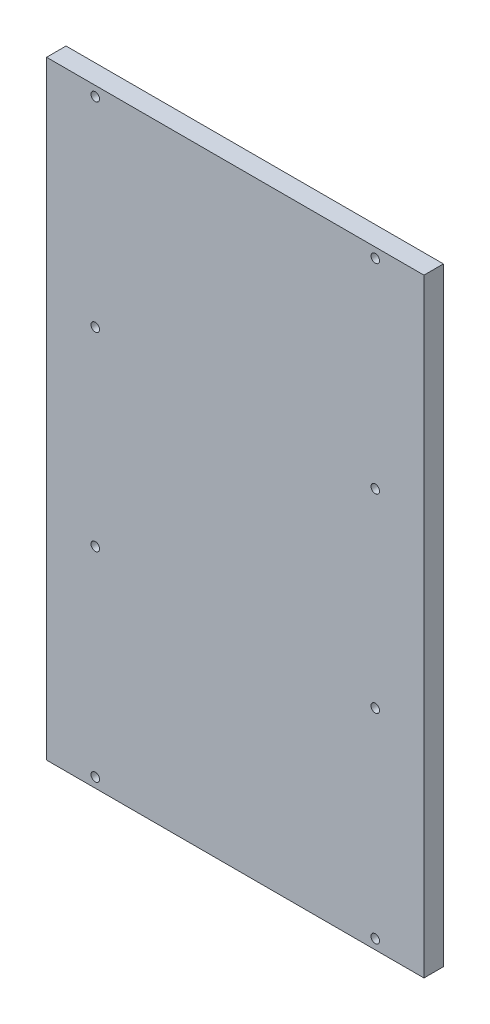
SolidWorks part; units mm, degrees
material "ДСП"
ref_plane "Спереди" through (0, 0, 0) normal (0, 0, 1) x (1, 0, 0)
ref_plane "Сверху" through (0, 0, 0) normal (0, 1, 0) x (1, 0, 0)
ref_plane "Справа" through (0, 0, 0) normal (1, 0, 0) x (0, 0, -1)
sketch "Эскиз1" plane through (0, 0, 0) normal (0, 0, 1) x (1, 0, 0)
  line L1 (0, 0) -> (310, 0)
  line L2 (0, 0) -> (0, 500)
  line L3 (0, 500) -> (310, 500)
  line L4 (310, 0) -> (310, 500)
  dimension "D1" = 500
  dimension "D2" = 310
extrude "Придание толщины" add sketch "Эскиз1" along normal blind 16
sketch "Эскиз3" plane through (0, 0, 16) normal (0, 0, 1) x (1, 0, 0)
  line L0 (0, 500) -> (0, 0) construction
  line L1 (0, 0) -> (310, 0) construction
  circle A0 centre (40, 8) radius 3.5
  dimension "D1" = 7
  dimension "D2" = 40
  dimension "D3" = 8
extrude "Отверстие 1" cut sketch "Эскиз3" against normal blind 16
sketch "Эскиз4" plane through (0, 0, 16) normal (0, 0, 1) x (1, 0, 0)
  line L0 (0, 500) -> (0, 0) construction
  line L1 (0, 0) -> (310, 0) construction
  circle A0 centre (270, 8) radius 3.5
  dimension "D3" = 7
  dimension "D1" = 270
  dimension "D2" = 8
extrude "Отверстие 2" cut sketch "Эскиз4" against normal blind 16
sketch "Эскиз5" plane through (0, 0, 16) normal (0, 0, 1) x (1, 0, 0)
  line L0 (0, 500) -> (0, 0) construction
  line L1 (0, 0) -> (310, 0) construction
  circle A0 centre (40, 492) radius 3.5
  dimension "D1" = 7
  dimension "D2" = 40
  dimension "D3" = 492
extrude "Отверстие 3" cut sketch "Эскиз5" against normal blind 16
sketch "Эскиз6" plane through (0, 0, 16) normal (0, 0, 1) x (1, 0, 0)
  line L0 (0, 500) -> (0, 0) construction
  line L1 (0, 0) -> (310, 0) construction
  circle A0 centre (270, 492) radius 3.5
  dimension "D1" = 7
  dimension "D3" = 492
  dimension "D2" = 270
extrude "Отверстие 4" cut sketch "Эскиз6" against normal blind 16
sketch "Эскиз7" plane through (0, 0, 16) normal (0, 0, 1) x (1, 0, 0)
  line L0 (0, 500) -> (0, 0) construction
  line L1 (0, 0) -> (310, 0) construction
  circle A0 centre (40, 172) radius 3.5
  dimension "D1" = 7
  dimension "D2" = 40
  dimension "D3" = 172
extrude "Отверстие 5" cut sketch "Эскиз7" against normal blind 16
sketch "Эскиз8" plane through (0, 0, 16) normal (0, 0, 1) x (1, 0, 0)
  line L0 (0, 500) -> (0, 0) construction
  line L1 (0, 0) -> (310, 0) construction
  circle A0 centre (270, 172) radius 3.5
  dimension "D1" = 7
  dimension "D2" = 270
  dimension "D3" = 172
extrude "Отверстие 6" cut sketch "Эскиз8" against normal blind 16
sketch "Эскиз9" plane through (0, 0, 16) normal (0, 0, 1) x (1, 0, 0)
  line L0 (0, 500) -> (0, 0) construction
  line L1 (0, 0) -> (310, 0) construction
  circle A0 centre (40, 328) radius 3.5
  dimension "D1" = 7
  dimension "D2" = 40
  dimension "D3" = 328
extrude "Отверстие 7" cut sketch "Эскиз9" against normal blind 16
sketch "Эскиз10" plane through (0, 0, 16) normal (0, 0, 1) x (1, 0, 0)
  line L0 (0, 500) -> (0, 0) construction
  line L1 (0, 0) -> (310, 0) construction
  circle A0 centre (270, 328) radius 3.5
  dimension "D1" = 7
  dimension "D2" = 270
  dimension "D3" = 328
extrude "Отверстие 8" cut sketch "Эскиз10" against normal blind 16
sketch "Эскиз27" plane through (0, 0, 16) normal (0, 0, 1) x (1, 0, 0)
  line L2 (0, 500) -> (0, 0) construction
  line L3 (0, 0) -> (310, 0) construction
  circle A0 centre (0, 0) radius 4
  dimension "D3" = 0
  dimension "D1" = 8
extrude "Отверстие 9" [suppressed] cut sketch "Эскиз27" against normal blind 10
sketch "Эскиз29" plane through (0, 0, 16) normal (0, 0, 1) x (1, 0, 0)
  line L2 (0, 500) -> (0, 0) construction
  line L3 (0, 0) -> (310, 0) construction
  circle A0 centre (0, 0) radius 4
  dimension "D1" = 8
extrude "Отверстие 10" [suppressed] cut sketch "Эскиз29" against normal blind 10
sketch "Эскиз30" plane through (0, 0, 16) normal (0, 0, 1) x (1, 0, 0)
  line L1 (0, 0) -> (310, 0) construction
  line L3 (0, 500) -> (0, 0) construction
  circle A0 centre (0, 0) radius 4
  dimension "D1" = 8
extrude "Отверстие 11" [suppressed] cut sketch "Эскиз30" against normal blind 10
sketch "Эскиз31" plane through (0, 0, 16) normal (0, 0, 1) x (1, 0, 0)
  line L2 (0, 0) -> (310, 0) construction
  line L3 (0, 500) -> (0, 0) construction
  circle A0 centre (0, 0) radius 4
  dimension "D1" = 8
extrude "Отверстие 12" [suppressed] cut sketch "Эскиз31" against normal blind 10
sketch "Эскиз11" plane through (0, 500, 0) normal (0, 1, 0) x (1, 0, 0)
  line L0 (0, -16) -> (0, 0) construction
  line L1 (310, -16) -> (0, -16) construction
  circle A0 centre (0, -16) radius 2.5
  dimension "D1" = 5
  dimension "D3" = 0
extrude "Отверстие А1" [suppressed] cut sketch "Эскиз11" against normal blind 37
sketch "Эскиз12" plane through (0, 500, 0) normal (0, 1, 0) x (1, 0, 0)
  line L1 (0, -16) -> (0, 0) construction
  line L2 (310, -16) -> (0, -16) construction
  circle A0 centre (0, -16) radius 2.5
  dimension "D1" = 5
  dimension "D3" = 0
extrude "Отверстие А2" [suppressed] cut sketch "Эскиз12" against normal blind 37
sketch "Эскиз13" plane through (0, 500, 0) normal (0, 1, 0) x (1, 0, 0)
  line L1 (0, -16) -> (0, 0) construction
  line L2 (310, -16) -> (0, -16) construction
  circle A0 centre (0, -16) radius 4
  dimension "D3" = 0
  dimension "D1" = 8
extrude "Отверстие А3" [suppressed] cut sketch "Эскиз13" against normal blind 20
sketch "Эскиз14" plane through (0, 500, 0) normal (0, 1, 0) x (1, 0, 0)
  line L0 (0, -16) -> (0, 0) construction
  line L1 (310, -16) -> (0, -16) construction
  circle A0 centre (0, -8) radius 4
  dimension "D3" = 8
  dimension "D1" = 8
extrude "Отверстие А4" [suppressed] cut sketch "Эскиз14" against normal blind 20
sketch "Эскиз15" plane through (310, 0, 0) normal (1, 0, 0) x (0, 0, -1)
  line L0 (-16, 500) -> (0, 500) construction
  line L1 (-16, 0) -> (-16, 500) construction
  circle A0 centre (-16, 500) radius 2.5
  dimension "D1" = 5
  dimension "D2" = 0
  dimension "D3" = 0
extrude "Отверстие В1" [suppressed] cut sketch "Эскиз15" against normal blind 37
sketch "Эскиз16" plane through (310, 0, 0) normal (1, 0, 0) x (0, 0, -1)
  line L0 (-16, 500) -> (0, 500) construction
  line L1 (-16, 0) -> (-16, 500) construction
  circle A0 centre (-16, 500) radius 2.5
  dimension "D1" = 5
extrude "Отверстие В2" [suppressed] cut sketch "Эскиз16" against normal blind 37
sketch "Эскиз17" plane through (310, 0, 0) normal (1, 0, 0) x (0, 0, -1)
  line L1 (-16, 500) -> (0, 500) construction
  line L2 (-16, 0) -> (-16, 500) construction
  circle A0 centre (-16, 500) radius 4
  dimension "D2" = 0
  dimension "D3" = 0
  dimension "D1" = 8
extrude "Отверстие В3" [suppressed] cut sketch "Эскиз17" against normal blind 20
sketch "Эскиз18" plane through (310, 0, 0) normal (1, 0, 0) x (0, 0, -1)
  line L0 (-16, 500) -> (0, 500) construction
  line L1 (-16, 0) -> (-16, 500) construction
  circle A0 centre (-16, 500) radius 4
  dimension "D2" = 8
  dimension "D3" = 0
  dimension "D1" = 0
extrude "Отверстие В4" [suppressed] cut sketch "Эскиз18" against normal blind 20
sketch "Эскиз19" plane through (0, 0, 0) normal (0, -1, 0) x (1, 0, 0)
  line L0 (310, 16) -> (310, 0) construction
  line L1 (0, 16) -> (310, 16) construction
  circle A0 centre (310, 16) radius 2.5
  dimension "D1" = 5
  dimension "D2" = 0
  dimension "D3" = 0
extrude "Отверстие С1" [suppressed] cut sketch "Эскиз19" against normal blind 37
sketch "Эскиз20" plane through (0, 0, 0) normal (0, -1, 0) x (1, 0, 0)
  line L0 (310, 16) -> (310, 0) construction
  line L1 (0, 16) -> (310, 16) construction
  circle A0 centre (310, 16) radius 2.5
  dimension "D3" = 0
  dimension "D1" = 0
  dimension "D2" = 5
extrude "Отверстие С2" [suppressed] cut sketch "Эскиз20" against normal blind 37
sketch "Эскиз21" plane through (0, 0, 0) normal (0, -1, 0) x (1, 0, 0)
  line L0 (310, 16) -> (310, 0) construction
  line L1 (0, 16) -> (310, 16) construction
  circle A0 centre (310, 16) radius 4
  dimension "D2" = 0
  dimension "D3" = 0
  dimension "D1" = 8
extrude "Отверстие С3" [suppressed] cut sketch "Эскиз21" against normal blind 20
sketch "Эскиз22" plane through (0, 0, 0) normal (0, -1, 0) x (1, 0, 0)
  line L0 (310, 16) -> (310, 0) construction
  line L1 (0, 16) -> (310, 16) construction
  circle A0 centre (310, 16) radius 4
  dimension "D2" = 0
  dimension "D3" = 0
  dimension "D1" = 8
extrude "Отверстие С4" [suppressed] cut sketch "Эскиз22" against normal blind 20
sketch "Эскиз23" plane through (0, 0, 0) normal (-1, 0, 0) x (0, 0, 1)
  line L0 (16, 0) -> (0, 0) construction
  line L1 (16, 500) -> (16, 0) construction
  circle A0 centre (16, 0) radius 2.5
  dimension "D1" = 5
  dimension "D2" = 0
  dimension "D3" = 0
extrude "Отверстие Д1" [suppressed] cut sketch "Эскиз23" against normal blind 37
sketch "Эскиз24" plane through (0, 0, 0) normal (-1, 0, 0) x (0, 0, 1)
  line L0 (16, 0) -> (0, 0) construction
  line L1 (16, 500) -> (16, 0) construction
  circle A0 centre (16, 0) radius 2.5
  dimension "D1" = 5
  dimension "D2" = 0
  dimension "D3" = 0
extrude "Отверстие Д2" [suppressed] cut sketch "Эскиз24" against normal blind 37
sketch "Эскиз25" plane through (0, 0, 0) normal (-1, 0, 0) x (0, 0, 1)
  line L0 (16, 0) -> (0, 0) construction
  line L1 (16, 500) -> (16, 0) construction
  circle A0 centre (16, 0) radius 4
  dimension "D2" = 0
  dimension "D3" = 0
  dimension "D1" = 8
extrude "Отверстие Д3" [suppressed] cut sketch "Эскиз25" against normal blind 20
sketch "Эскиз26" plane through (0, 0, 0) normal (-1, 0, 0) x (0, 0, 1)
  line L0 (16, 0) -> (0, 0) construction
  line L1 (16, 500) -> (16, 0) construction
  circle A0 centre (16, 0) radius 4
  dimension "D2" = 0
  dimension "D3" = 0
  dimension "D1" = 8
extrude "Отверстие Д4" [suppressed] cut sketch "Эскиз26" against normal blind 20
equation "\"D1@Придание толщины\" = \"Thick\""
equation "\"D2@Эскиз1\"=\"Width\""
equation "\"D1@Эскиз1\"=\"Height\""
equation "\"D1\" = 7"
equation "\"X1\" = 40"
equation "\"Y1\" = 8"
equation "\"H1\" = 16"
equation "\"D1@Эскиз3\"=\"D1\""
equation "\"D2@Эскиз3\"=\"X1\""
equation "\"D3@Эскиз3\"=\"Y1\""
equation "\"D1@Отверстие 1\"=\"H1\""
equation "\"D2\" = 7"
equation "\"X2\" = 270"
equation "\"Y2\" = 8"
equation "\"H2\" = 16"
equation "\"D3\" = 7"
equation "\"X3\" = 40"
equation "\"Y3\" = 492"
equation "\"H3\" = 16"
equation "\"D4\" = 7"
equation "\"X4\" = 270"
equation "\"Y4\" = 492"
equation "\"H4\" = 16"
equation "\"D5\" = 7"
equation "\"X5\" = 40"
equation "\"Y5\" = 172"
equation "\"H5\" = 16"
equation "\"D6\" = 7"
equation "\"X6\" = 270"
equation "\"Y6\" = 172"
equation "\"H6\" = 16"
equation "\"D7\" = 7"
equation "\"X7\" = 40"
equation "\"Y7\" = 328"
equation "\"H7\" = 16"
equation "\"D8\" = 7"
equation "\"X8\" = 270"
equation "\"Y8\" = 328"
equation "\"H8\" = 16"
equation "\"D3@Эскиз4\"=\"D2\""
equation "\"D1@Эскиз4\"=\"X2\""
equation "\"D2@Эскиз4\"=\"Y2\""
equation "\"D1@Отверстие 2\"=\"H2\""
equation "\"D2@Эскиз5\"=\"X3\""
equation "\"D1@Эскиз5\"=\"D3\""
equation "\"D3@Эскиз5\"=\"Y3\""
equation "\"D1@Отверстие 3\" = \"H3\""
equation "\"D1@Эскиз6\"=\"D4\""
equation "\"D2@Эскиз6\"=\"X4\""
equation "\"D3@Эскиз6\"=\"Y4\""
equation "\"D1@Отверстие 4\" = \"H4\""
equation "\"D1@Эскиз7\"=\"D5\""
equation "\"D2@Эскиз7\"=\"X5\""
equation "\"D3@Эскиз7\"=\"Y5\""
equation "\"D1@Отверстие 5\" = \"H5\""
equation "\"D1@Эскиз8\"=\"D6\""
equation "\"D2@Эскиз8\"=\"X6\""
equation "\"D3@Эскиз8\"=\"Y6\""
equation "\"D1@Отверстие 6\" = \"H6\""
equation "\"D1@Эскиз9\"=\"D7\""
equation "\"D2@Эскиз9\"=\"X7\""
equation "\"D3@Эскиз9\"=\"Y7\""
equation "\"D1@Отверстие 7\" = \"H7\""
equation "\"D1@Эскиз10\"=\"D8\""
equation "\"D2@Эскиз10\"=\"X8\""
equation "\"D3@Эскиз10\"=\"Y8\""
equation "\"D1@Отверстие 8\" = \"H8\""
equation "\"Отверстие 1\"= IIF ( \"D1\" = 0 , \"suppressed\" , \"unsuppressed\" )"
equation "\"Отверстие 2\"= IIF ( \"D2\" = 0 , \"suppressed\" , \"unsuppressed\" )"
equation "\"Отверстие 3\"= IIF ( \"D3\" = 0 , \"suppressed\" , \"unsuppressed\" )"
equation "\"Отверстие 4\"= IIF ( \"D4\" = 0 , \"suppressed\" , \"unsuppressed\" )"
equation "\"Отверстие 5\"= IIF ( \"D5\" = 0 , \"suppressed\" , \"unsuppressed\" )"
equation "\"Отверстие 6\" = IIF ( \"D6\" = 0 , \"suppressed\" , \"unsuppressed\" )"
equation "\"Отверстие 7\"= IIF ( \"D7\" = 0 , \"suppressed\" , \"unsuppressed\" )"
equation "\"Отверстие 8\"= IIF ( \"D8\" = 0 , \"suppressed\" , \"unsuppressed\" )"
equation "\"DA1\" = 0"
equation "\"XA1\" = 0"
equation "\"YA1\" = 0"
equation "\"HA1\" = 0"
equation "\"DA2\" = 0"
equation "\"XA2\" = 0"
equation "\"YA2\" = 0"
equation "\"HA2\" = 0"
equation "\"DA3\" = 0"
equation "\"XA3\" = 0"
equation "\"YA3\" = 0"
equation "\"DA4\" = 0"
equation "\"XA4\" = 0"
equation "\"YA4\" = 0"
equation "\"HA4\" = 0"
equation "\"D1@Эскиз11\"=\"DA1\""
equation "\"D2@Эскиз11\"=\"XA1\""
equation "\"D3@Эскиз11\"=\"YA1\""
equation "\"D1@Отверстие А1\" = \"HA1\""
equation "\"D1@Эскиз12\"=\"DA2\""
equation "\"D2@Эскиз12\"=\"XA2\""
equation "\"HA3\" = 0"
equation "\"D1@Эскиз13\"=\"DA3\""
equation "\"D2@Эскиз13\"=\"XA3\""
equation "\"D3@Эскиз13\"=\"YA3\""
equation "\"D1@Отверстие А3\" = \"HA3\""
equation "\"D1@Отверстие А2\" = \"HA2\""
equation "\"D1@Эскиз14\"=\"DA4\""
equation "\"D2@Эскиз14\"=\"XA4\""
equation "\"Отверстие А1\"= IIF ( \"DA1\" = 0 , \"suppressed\" , \"unsuppressed\" )"
equation "\"Отверстие А2\"= IIF ( \"DA2\" = 0 , \"suppressed\" , \"unsuppressed\" )"
equation "\"Отверстие А3\"= IIF ( \"DA3\" = 0 , \"suppressed\" , \"unsuppressed\" )"
equation "\"Отверстие А4\"= IIF ( \"DA4\" = 0 , \"suppressed\" , \"unsuppressed\" )"
equation "\"DB1\" = 0"
equation "\"XB1\" = 0"
equation "\"YB1\" = 0"
equation "\"HB1\" = 0"
equation "\"DB2\" = 0"
equation "\"XB2\" = 0"
equation "\"YB2\" = 0"
equation "\"HB2\" = 0"
equation "\"DB3\" = 0"
equation "\"XB3\" = 0"
equation "\"YB3\" = 0"
equation "\"HB3\" = 0"
equation "\"DB4\" = 0"
equation "\"XB4\" = 0"
equation "\"YB4\" = 0"
equation "\"HB4\" = 0"
equation "\"DC1\" = 0"
equation "\"XC1\" = 0"
equation "\"YC1\" = 0"
equation "\"HC1\" = 0"
equation "\"DC2\" = 0"
equation "\"XC2\" = 0"
equation "\"YC2\" = 0"
equation "\"HC2\" = 0"
equation "\"DC3\" = 0"
equation "\"XC3\" = 0"
equation "\"YC3\" = 0"
equation "\"HC3\" = 0"
equation "\"DC4\" = 0"
equation "\"XC4\" = 0"
equation "\"YC4\" = 0"
equation "\"HC4\" = 0"
equation "\"DD1\" = 0"
equation "\"XD1\" = 0"
equation "\"YD1\" = 0"
equation "\"HD1\" = 0"
equation "\"DD2\" = 0"
equation "\"XD2\" = 0"
equation "\"YD2\" = 0"
equation "\"HD2\" = 0"
equation "\"DD3\" = 0"
equation "\"XD3\" = 0"
equation "\"YD3\" = 0"
equation "\"HD3\" = 0"
equation "\"DD4\" = 0"
equation "\"XD4\" = 0"
equation "\"YD4\" = 0"
equation "\"HD4\" = 0"
equation "\"D1@Эскиз15\"=\"DB1\""
equation "\"D2@Эскиз15\"=\"XB1\""
equation "\"D3@Эскиз15\"=\"YB1\""
equation "\"D1@Отверстие В1\" = \"HB1\""
equation "\"D1@Эскиз16\"=\"DB2\""
equation "\"D2@Эскиз16\"=\"XB2\""
equation "\"D3@Эскиз16\"=\"YB2\""
equation "\"D1@Отверстие В2\" = \"HB2\""
equation "\"D1@Эскиз17\"=\"DB3\""
equation "\"D2@Эскиз17\"=\"XB3\""
equation "\"D3@Эскиз17\"=\"YB3\""
equation "\"D1@Отверстие В3\" = \"HB3\""
equation "\"D1@Эскиз18\"=\"XB4\""
equation "\"D2@Эскиз18\"=\"DB4\""
equation "\"D3@Эскиз18\"=\"YB4\""
equation "\"D1@Отверстие В4\" = \"HB4\""
equation "\"D1@Эскиз19\"=\"DC1\""
equation "\"D2@Эскиз19\"=\"XC1\""
equation "\"D3@Эскиз19\"=\"YC1\""
equation "\"D1@Отверстие С1\" = \"HC1\""
equation "\"D1@Эскиз20\"=\"XC2\""
equation "\"D2@Эскиз20\"=\"DC2\""
equation "\"D3@Эскиз20\"=\"YC2\""
equation "\"D1@Отверстие С2\" = \"HC2\""
equation "\"D1@Эскиз21\"=\"DC3\""
equation "\"D2@Эскиз21\"=\"XC3\""
equation "\"D3@Эскиз21\"=\"YC3\""
equation "\"D1@Отверстие С3\" = \"HC3\""
equation "\"D1@Эскиз22\"=\"DC4\""
equation "\"D2@Эскиз22\"=\"XC4\""
equation "\"D3@Эскиз22\"=\"YC4\""
equation "\"D1@Отверстие С4\" = \"HC4\""
equation "\"D1@Эскиз23\"=\"DD1\""
equation "\"D2@Эскиз23\"=\"XD1\""
equation "\"D3@Эскиз23\"=\"YD1\""
equation "\"D1@Отверстие Д1\" = \"HD1\""
equation "\"D1@Эскиз24\"=\"DD2\""
equation "\"D2@Эскиз24\"=\"XD2\""
equation "\"D3@Эскиз24\"=\"YD2\""
equation "\"D1@Отверстие Д2\" = \"HD2\""
equation "\"D1@Эскиз25\"=\"DD3\""
equation "\"D2@Эскиз25\"=\"XD3\""
equation "\"D3@Эскиз25\"=\"YD3\""
equation "\"D1@Отверстие Д3\" = \"HD3\""
equation "\"D1@Эскиз26\"=\"DD4\""
equation "\"D2@Эскиз26\"=\"XD4\""
equation "\"D3@Эскиз26\"=\"YD4\""
equation "\"D1@Отверстие Д4\" = \"HD4\""
equation "\"Отверстие В1\"= IIF ( \"DB1\" = 0 , \"suppressed\" , \"unsuppressed\" )"
equation "\"Отверстие В2\"= IIF ( \"DB2\" = 0 , \"suppressed\" , \"unsuppressed\" )"
equation "\"Отверстие В3\"= IIF ( \"DB3\" = 0 , \"suppressed\" , \"unsuppressed\" )"
equation "\"Отверстие В4\"= IIF ( \"DB4\" = 0 , \"suppressed\" , \"unsuppressed\" )"
equation "\"Отверстие С1\"= IIF ( \"DC1\" = 0 , \"suppressed\" , \"unsuppressed\" )"
equation "\"Отверстие С2\"= IIF ( \"DC2\" = 0 , \"suppressed\" , \"unsuppressed\" )"
equation "\"Отверстие С3\"= IIF ( \"DC3\" = 0 , \"suppressed\" , \"unsuppressed\" )"
equation "\"Отверстие С4\"= IIF ( \"DC4\" = 0 , \"suppressed\" , \"unsuppressed\" )"
equation "\"Отверстие Д1\"= IIF ( \"DD1\" = 0 , \"suppressed\" , \"unsuppressed\" )"
equation "\"Отверстие Д2\"= IIF ( \"DD2\" = 0 , \"suppressed\" , \"unsuppressed\" )"
equation "\"Отверстие Д3\"= IIF ( \"DD3\" = 0 , \"suppressed\" , \"unsuppressed\" )"
equation "\"Отверстие Д4\"= IIF ( \"DD4\" = 0 , \"suppressed\" , \"unsuppressed\" )"
equation "\"D9\" = 0"
equation "\"X9\" = 0"
equation "\"Y9\" = 0"
equation "\"H9\" = 0"
equation "\"D10\" = 0"
equation "\"X10\" = 0"
equation "\"Y10\" = 0"
equation "\"H10\" = 0"
equation "\"D11\" = 0"
equation "\"X11\" = 0"
equation "\"Y11\" = 0"
equation "\"H11\" = 0"
equation "\"D12\" = 0"
equation "\"X12\" = 0"
equation "\"Y12\" = 0"
equation "\"H12\" = 0"
equation "\"D1@Эскиз27\"=\"D9\""
equation "\"D2@Эскиз27\"=\"X9\""
equation "\"D3@Эскиз27\"=\"Y9\""
equation "\"D1@Отверстие 9\" = \"H9\""
equation "\"D1@Эскиз29\"=\"D10\""
equation "\"D2@Эскиз29\"=\"X10\""
equation "\"D3@Эскиз29\"=\"Y10\""
equation "\"D1@Отверстие 10\" = \"H10\""
equation "\"D1@Эскиз30\"=\"D11\""
equation "\"D2@Эскиз30\"=\"X11\""
equation "\"D3@Эскиз30\"=\"Y11\""
equation "\"D1@Отверстие 11\" = \"H11\""
equation "\"D1@Эскиз31\"=\"D12\""
equation "\"D2@Эскиз31\"=\"X12\""
equation "\"D3@Эскиз31\"=\"Y12\""
equation "\"D1@Отверстие 12\" = \"H12\""
equation "\"Отверстие 9\"= IIF ( \"D9\" = 0 , \"suppressed\" , \"unsuppressed\" )"
equation "\"Отверстие 10\"= IIF ( \"D10\" = 0 , \"suppressed\" , \"unsuppressed\" )"
equation "\"Отверстие 11\"= IIF ( \"D11\" = 0 , \"suppressed\" , \"unsuppressed\" )"
equation "\"Отверстие 12\"= IIF ( \"D12\" = 0 , \"suppressed\" , \"unsuppressed\" )"
equation "\"Height\" = 500"
equation "\"Width\" = 310"
equation "\"Thick\" = 16"
equation "\"D3@Эскиз12\"=\"YA2\""
